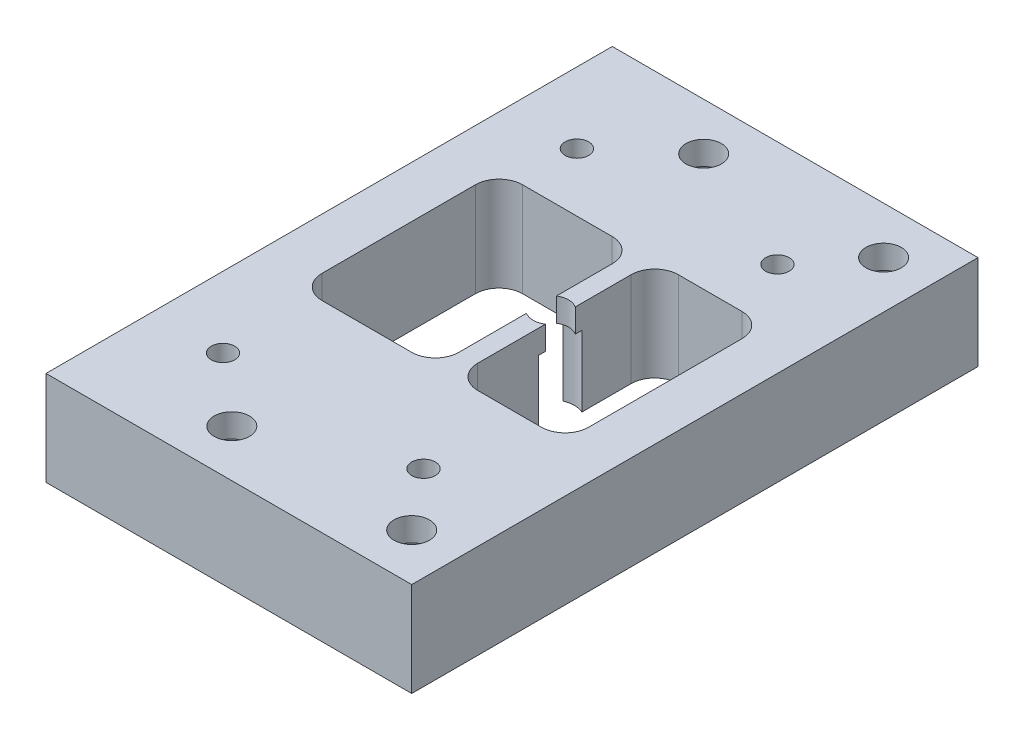
SolidWorks part; units mm, degrees
material "K110"
ref_plane "Front Plane" through (0, 0, 0) normal (0, 0, 1) x (1, 0, 0)
ref_plane "Top Plane" through (0, 0, 0) normal (0, 1, 0) x (1, 0, 0)
ref_plane "Right Plane" through (0, 0, 0) normal (1, 0, 0) x (0, 0, -1)
sketch "Sketch1" plane through (0, 0, 0) normal (0, 1, 0) x (1, 0, 0)
  line L1 (-77.5, 120) -> (77.5, 120)
  line L2 (-77.5, 120) -> (-77.5, -120)
  line L3 (-77.5, -120) -> (77.5, -120)
  line L4 (77.5, 120) -> (77.5, -120)
  line L5 (-77.5, 120) -> (77.5, -120) construction
  line L6 (-77.5, -120) -> (77.5, 120) construction
  point P0 (0, 0)
  dimension "D1" = 240
  dimension "D2" = 155
extrude "Boss-Extrude1" add sketch "Sketch1" against normal blind 40
sketch "Sketch2" plane through (0, 0, 0) normal (0, 1, 0) x (1, 0, 0)
  line L3 (25.25, -27.27) -> (25.25, -11.27) construction
  line L4 (28.25, -8.27) -> (34.38, -8.27) construction
  line L5 (36.38, -6.27) -> (36.38, 11.73) construction
  line L6 (34.38, 13.73) -> (28.25, 13.73) construction
  line L7 (25.25, 42.73) -> (25.25, 16.73) construction
  line L8 (-36.87, 42.73) -> (-12.75, 42.73) construction
  line L9 (-12.75, 42.73) -> (-12.75, 34.23) construction
  line L10 (-14.25, 32.73) -> (-28.87, 32.73) construction
  line L11 (-34.87, 26.73) -> (-34.87, -6.27) construction
  line L12 (-28.87, -12.27) -> (-14.25, -12.27) construction
  line L13 (-12.75, -27.27) -> (-12.75, -13.77) construction
  line L14 (-36.87, -27.27) -> (-12.75, -27.27) construction
  line L15 (-39.87, 39.73) -> (-39.87, -24.27) construction
  line L19 (25.25, -27.27) -> (25.25, -11.27)
  line L20 (28.25, -8.27) -> (34.38, -8.27)
  line L21 (36.38, -6.27) -> (36.38, 11.73)
  line L22 (34.38, 13.73) -> (28.25, 13.73)
  line L23 (25.25, 42.73) -> (25.25, 16.73)
  line L24 (-36.87, 42.73) -> (-12.75, 42.73)
  line L25 (-12.75, 42.73) -> (-12.75, 34.23)
  line L26 (-14.25, 32.73) -> (-28.87, 32.73)
  line L27 (-34.87, 26.73) -> (-34.87, -6.27)
  line L28 (-28.87, -12.27) -> (-14.25, -12.27)
  line L29 (-12.75, -27.27) -> (-12.75, -13.77)
  line L30 (-36.87, -27.27) -> (-12.75, -27.27)
  line L31 (-39.87, 39.73) -> (-39.87, -24.27)
  line L32 (40.88, 42.73) -> (41.38, 39.73) construction
  line L33 (38.38, 42.73) -> (40.88, 42.73) construction
  line L34 (40.88, -27.27) -> (38.38, -27.27) construction
  line L35 (41.38, -24.27) -> (40.88, -27.27) construction
  line L36 (25.25, 42.73) -> (38.38, 42.73) construction
  line L37 (41.38, 39.73) -> (41.38, -24.27) construction
  line L38 (38.38, -27.27) -> (25.25, -27.27) construction
  line L39 (25.25, 42.73) -> (38.38, 42.73)
  line L40 (41.38, 39.73) -> (41.38, -24.27)
  line L41 (38.38, -27.27) -> (25.25, -27.27)
  arc A0 (28.25, -8.27) -> (25.25, -11.27) centre (28.25, -11.27) ccw construction
  arc A1 (34.38, -8.27) -> (36.38, -6.27) centre (34.38, -6.27) ccw construction
  arc A2 (36.38, 11.73) -> (34.38, 13.73) centre (34.38, 11.73) ccw construction
  arc A3 (25.25, 16.73) -> (28.25, 13.73) centre (28.25, 16.73) ccw construction
  arc A4 (-36.87, 42.73) -> (-39.87, 39.73) centre (-36.87, 39.73) ccw construction
  arc A5 (-14.25, 32.73) -> (-12.75, 34.23) centre (-14.25, 34.23) ccw construction
  arc A6 (-28.87, 32.73) -> (-34.87, 26.73) centre (-28.87, 26.73) ccw construction
  arc A7 (-34.87, -6.27) -> (-28.87, -12.27) centre (-28.87, -6.27) ccw construction
  arc A8 (-12.75, -13.77) -> (-14.25, -12.27) centre (-14.25, -13.77) ccw construction
  arc A9 (-39.87, -24.27) -> (-36.87, -27.27) centre (-36.87, -24.27) ccw construction
  arc A10 (28.25, -8.27) -> (25.25, -11.27) centre (28.25, -11.27) ccw
  arc A11 (34.38, -8.27) -> (36.38, -6.27) centre (34.38, -6.27) ccw
  arc A12 (36.38, 11.73) -> (34.38, 13.73) centre (34.38, 11.73) ccw
  arc A13 (25.25, 16.73) -> (28.25, 13.73) centre (28.25, 16.73) ccw
  arc A14 (-36.87, 42.73) -> (-39.87, 39.73) centre (-36.87, 39.73) ccw
  arc A15 (-14.25, 32.73) -> (-12.75, 34.23) centre (-14.25, 34.23) ccw
  arc A16 (-28.87, 32.73) -> (-34.87, 26.73) centre (-28.87, 26.73) ccw
  arc A17 (-34.87, -6.27) -> (-28.87, -12.27) centre (-28.87, -6.27) ccw
  arc A18 (-12.75, -13.77) -> (-14.25, -12.27) centre (-14.25, -13.77) ccw
  arc A19 (-39.87, -24.27) -> (-36.87, -27.27) centre (-36.87, -24.27) ccw
  arc A20 (41.38, 39.73) -> (38.38, 42.73) centre (38.38, 39.73) ccw construction
  arc A21 (38.38, -27.27) -> (41.38, -24.27) centre (38.38, -24.27) ccw construction
  arc A22 (41.38, 39.73) -> (38.38, 42.73) centre (38.38, 39.73) ccw
  arc A23 (38.38, -27.27) -> (41.38, -24.27) centre (38.38, -24.27) ccw
sketch "Sketch3" plane through (0, 0, 0) normal (0, 1, 0) x (1, 0, 0)
  line L1 (-55.75, 50.23) -> (2.25, 50.23)
  line L2 (-55.75, 50.23) -> (-55.75, -34.77)
  line L3 (-55.75, -34.77) -> (2.25, -34.77)
  line L4 (2.25, 50.23) -> (2.25, -34.77)
  line L5 (10.25, 50.23) -> (57.25, 50.23)
  line L6 (10.25, 50.23) -> (10.25, -34.77)
  line L7 (10.25, -34.77) -> (57.25, -34.77)
  line L8 (57.25, 50.23) -> (57.25, -34.77)
  line L15 (25.25, 42.73) -> (25.25, 16.73) construction
  line L16 (-12.75, 42.73) -> (-12.75, 34.23) construction
  dimension "D1" = 85
  dimension "D4" = 15
  dimension "D5" = 15
  dimension "D6" = 47
  dimension "D7" = 58
extrude "Cut-Extrude1" cut sketch "Sketch3" against normal up to next
fillet "Fillet1" radius 10 8 edges at (10.25, -20, -50.23) (57.25, -20, 34.77) (57.25, -20, -50.23) (10.25, -20, 34.77) (-55.75, -20, 34.77) (2.25, -20, 34.77) (2.25, -20, -50.23) (-55.75, -20, -50.23)
extrude "Cut-Extrude4" cut sketch "Sketch7" against normal through all
sketch "Sketch7" plane through (270.13, 0, 0) normal (0, 1, 0) x (1, 0, 0)
  circle A0 centre (-263.88, 10.23) radius 7.5
extrude "Cut-Extrude5" cut sketch "Sketch8" against normal blind 30
sketch "Sketch8" plane through (270.13, -40, 0) normal (0, -1, 0) x (1, 0, 0)
  circle A0 centre (-263.88, -10.23) radius 10
hole_wizard "M10 Tapped Hole1" positions "Sketch18" profile "Sketch10" tap size "M10" standard "ISO"
sketch "Sketch18" plane through (0, -40, 0) normal (0, -1, 0) x (-1, 0, 0)
  line L0 (-77.5, 120) -> (77.5, 120) construction
  line L1 (-77.5, -120) -> (-77.5, 120) construction
  line L2 (77.5, 120) -> (77.5, -120) construction
  line L3 (77.5, -120) -> (-77.5, -120) construction
  point P0 (-65, 75)
  point P2 (65, 75)
  point P4 (65, -75)
  point P6 (-65, -75)
  dimension "D1" = 45
  dimension "D2" = 12.5
  dimension "D3" = 12.5
  dimension "D4" = 45
sketch "Sketch10" plane through (65, -40, -75) normal (1, 0, 0) x (0, 0, -1)
  line L0 (0, 0) -> (0, 27.0537)
  line L1 (0, 27.0537) -> (4.25, 24.5)
  line L2 (4.25, 24.5) -> (4.25, 0)
  line L5 (4.25, 0) -> (0, 0)
  line L10 (0, 27.0537) -> (-4.25, 24.5) construction
  line L11 (0, -6.35) -> (0, 107.95) construction
  dimension "Tap Drill Dia." = 8.5
  dimension "Tap Drill Depth" = 24.5
  dimension "Drill Angle" = 118
cosmetic thread "Hole Thread1" parameters "D1"=20, "D2"=10
cosmetic thread "Hole Thread2" parameters "D1"=20, "D2"=10
cosmetic thread "Hole Thread3" parameters "D1"=20, "D2"=10
cosmetic thread "Hole Thread4" parameters "D1"=20, "D2"=10
hole_wizard "Ø10.0mm Dowel Hole1" positions "Sketch19" profile "Sketch13" hole size "Ø10.0" standard "ISO" end condition through all
sketch "Sketch19" plane through (0, -40, 0) normal (0, -1, 0) x (-1, 0, 0)
  line L0 (-77.5, -120) -> (-77.5, 120) construction
  line L1 (77.5, 120) -> (77.5, -120) construction
  line L2 (-77.5, 120) -> (77.5, 120) construction
  circle A2 centre (-65, -75) radius 4.25 construction
  point P0 (-37.5, 75)
  point P2 (-37.5, -75)
  point P4 (47.5, -75)
  point P6 (47.5, 75)
  point P20 (0, 0)
  dimension "D1" = 40
  dimension "D2" = 45
  dimension "D3" = 30
  dimension "D4" = 0
sketch "Sketch13" plane through (37.5, -40, -75) normal (1, 0, 0) x (0, 0, -1)
  line L0 (0, 0) -> (0, 40)
  line L1 (0, 40) -> (5, 40)
  line L2 (5, 40) -> (5, 0)
  line L5 (5, 0) -> (0, 0)
  line L11 (0, -6.35) -> (0, 107.95) construction
  dimension "Thru Hole Dia." = 10
  dimension "Thru Hole Depth" = 40
sketch "Sketch15" plane through (0, 0, 0) normal (0, 1, 0) x (1, 0, 0)
  line L0 (-192.37, -95) -> (270.13, -95) construction
  line L1 (77.5, -120) -> (77.5, 120) construction
  line L4 (-22, 0) -> (22, 0) construction
  circle A0 centre (57.5, -100) radius 7.5
  circle A1 centre (-18.75, -100) radius 7.5
  circle A2 centre (57.5, 100) radius 7.5
  circle A3 centre (-18.75, 100) radius 7.5
  point P6 (0, 0)
  dimension "D1" = 15
  dimension "D2" = 5
  dimension "D3" = 20
  dimension "D4" = 76.25
extrude "Cut-Extrude6" cut sketch "Sketch15" against normal up to next
sketch "Sketch16" plane through (0, -40, 0) normal (0, -1, 0) x (1, 0, 0)
  circle A0 centre (-18.75, -100) radius 9
  circle A1 centre (57.5, -100) radius 9
  circle A2 centre (57.5, 100) radius 9
  circle A3 centre (-18.75, 100) radius 9
  dimension "D1" = 18
extrude "Cut-Extrude7" cut sketch "Sketch16" against normal blind 30
